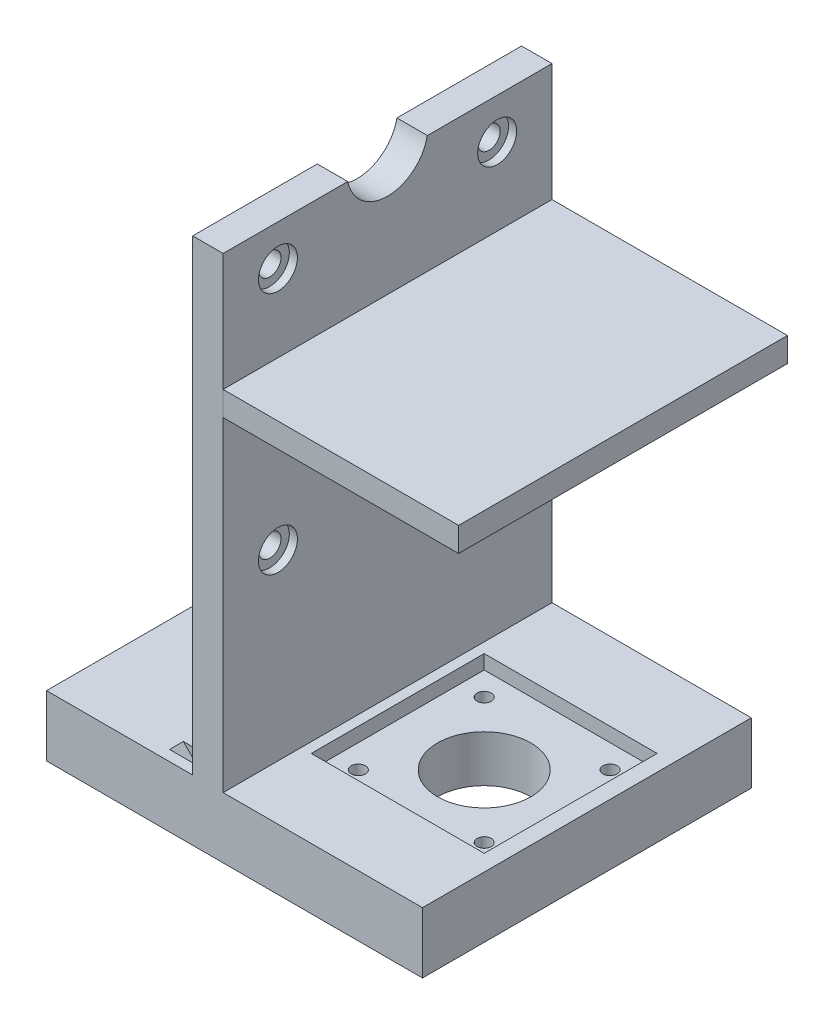
SolidWorks part; units mm, degrees
note: The reader was unsure of these and kept them because the rebuilt part matched: shared geometry of "Sketch11<5>", "Sketch13<3>", "Sketch21<2>".
ref_plane "Front Plane" through (0, 0, 0) normal (0, 0, 1) x (1, 0, 0)
ref_plane "Top Plane" through (0, 0, 0) normal (0, 1, 0) x (1, 0, 0)
ref_plane "Right Plane" through (0, 0, 0) normal (1, 0, 0) x (0, 0, -1)
sketch "Sketch1" plane through (0, 0, 0) normal (0, 1, 0) x (1, 0, 0)
  line L1 (-23.2, -27.5) -> (23.2, -27.5)
  line L2 (-23.2, -27.5) -> (-23.2, 27.5)
  line L3 (-23.2, 27.5) -> (23.2, 27.5)
  line L4 (23.2, -27.5) -> (23.2, 27.5)
  line L5 (-23.2, -27.5) -> (23.2, 27.5) construction
  line L6 (-23.2, 27.5) -> (23.2, -27.5) construction
  line L7 (-28.2, -33.5) -> (28.2, -33.5)
  line L8 (-28.2, -33.5) -> (-28.2, 33.5)
  line L9 (-28.2, 33.5) -> (28.2, 33.5)
  line L10 (28.2, -33.5) -> (28.2, 33.5)
  line L11 (-28.2, -33.5) -> (28.2, 33.5) construction
  line L12 (-28.2, 33.5) -> (28.2, -33.5) construction
  circle A0 centre (-2.9, 0) radius 4
  circle A1 centre (43.1, 0) radius 4
  point P0 (0, 0)
  point P6 (0, 0)
  dimension "D3" = 8
  dimension "D1" = 20.3
  dimension "D2" = 14.9
  dimension "D4" = 46
  dimension "D5" = 5
  dimension "D6" = 6
  dimension "D7" = 55
extrude "Boss-Extrude1" add sketch "Sketch1" along normal blind 14 contours L7 L10 L9 L8 L4 L1 L2 L3
sketch "Sketch4" plane through (0, 0, 0) normal (0, 1, 0) x (1, 0, 0)
  line L0 (-28.2, -33.5) -> (-40.2, -33.5)
  line L1 (-40.2, -33.5) -> (-40.2, -21.5)
  line L2 (-40.2, -21.5) -> (-28.2, -21.5)
  line L3 (-28.2, -33.5) -> (-28.2, 33.5) construction
  line L4 (-28.2, -21.5) -> (-28.2, -33.5)
  line L5 (-28.2, 33.5) -> (-40.2, 33.5)
  line L6 (-40.2, 33.5) -> (-40.2, 21.5)
  line L7 (-40.2, 21.5) -> (-28.2, 21.5)
  line L8 (-28.2, 21.5) -> (-28.2, 33.5)
  dimension "D1" = 12
  dimension "D2" = 12
extrude "Boss-Extrude2" add sketch "Sketch4" along normal blind 200
sketch "Sketch16" plane through (0, 0, -21.5) normal (0, 0, 1) x (1, 0, 0)
  line L0 (-40.2, 0) -> (-28.2, 0) construction
  line L1 (-28.2, 14) -> (-32.8, 14)
  line L2 (-28.2, 14) -> (-28.2, 0)
  line L3 (-28.2, 0) -> (-32.8, 0)
  line L4 (-32.8, 14) -> (-32.8, 0)
  dimension "D1" = 4.6
extrude "Boss-Extrude11" add sketch "Sketch16" along normal up to surface (43 mm away) up to face at (-33, 82.8, 21.5)
sketch "Sketch5" plane through (0, 200, 0) normal (0, 1, 0) x (1, 0, 0)
  line L0 (-28.2, -33.5) -> (28.2, -33.5) construction
  line L1 (-28.2, 33.5) -> (-23.2, 33.5)
  line L2 (-28.2, 33.5) -> (-28.2, -33.5)
  line L3 (-28.2, -33.5) -> (-23.2, -33.5)
  line L4 (-23.2, 33.5) -> (-23.2, -33.5)
  line L7 (-23.2, -27.5) -> (-23.2, 27.5) construction
extrude "Boss-Extrude3" add sketch "Sketch5" against normal blind 14
sketch "Sketch6" plane through (-40.2, 0, 0) normal (-1, 0, 0) x (0, 0, 1)
  line L0 (-21.5, 186) -> (21.5, 157.4103)
  line L1 (21.5, 200) -> (21.5, 0) construction
  line L2 (-21.5, 171.5897) -> (21.5, 143)
  line L3 (21.5, 143) -> (-21.5, 114.4103)
  line L4 (-21.5, 200) -> (-21.5, 0) construction
  line L5 (21.5, 128.5897) -> (-21.5, 100)
  line L6 (21.5, 157.4103) -> (21.5, 143)
  line L7 (21.5, 128.5897) -> (21.5, 143)
  line L8 (-21.5, 114.4103) -> (-21.5, 100)
  line L9 (-21.5, 186) -> (-21.5, 171.5897)
  line L10 (-21.5, 100) -> (21.5, 71.4103)
  line L11 (21.5, 71.4103) -> (21.5, 57)
  line L12 (21.5, 57) -> (-21.5, 85.5897)
  line L13 (-21.5, 85.5897) -> (-21.5, 100)
  line L14 (21.5, 57) -> (-21.5, 28.4103)
  line L15 (-21.5, 28.4103) -> (-21.5, 14)
  line L16 (-21.5, 14) -> (21.5, 42.5897)
  line L17 (21.5, 42.5897) -> (21.5, 57)
  line L18 (-21.5, 200) -> (-21.5, 186) construction
  line M18 (-21.5, 0) -> (-21.5, 200)
  dimension "D1" = 12
extrude "Boss-Extrude4" add sketch "Sketch6" against normal up to surface (12 mm away) contours L6 L0 L2 M18 | L5 L7 L3 M18 | L12 L11 L10 M18 | L16 L17 L14 M18 up to face at (-28.2, 100, 27.5)
sketch "Sketch2" plane through (28.2, 0, 0) normal (1, 0, 0) x (0, 0, -1)
  line L0 (-20.75, 7) -> (20.75, 7) construction
  line L1 (33.5, 14) -> (33.5, 0) construction
  circle A0 centre (-20.75, 7) radius 2.75
  circle A1 centre (20.75, 7) radius 2.75
  point P4 (33.5, 7)
  point P5 (0, 7)
  dimension "D1" = 5.5
  dimension "D2" = 41.5
extrude "Cut-Extrude1" cut sketch "Sketch2" against normal up to surface (5 mm away) up to face at (23.2, 7, 0)
sketch "Sketch3" plane through (-23.2, 0, 0) normal (1, 0, 0) x (0, 0, -1)
  line L0 (15.85, 7) -> (-15.85, 7) construction
  line L1 (-33.5, 14) -> (-33.5, 0) construction
  line L3 (-15.85, 7) -> (-33.5, 7) construction
  circle A0 centre (15.85, 7) radius 2.75
  circle A1 centre (-15.85, 7) radius 2.75
  point P0 (0, 7)
  dimension "D2" = 5.5
  dimension "D1" = 31.7
extrude "Cut-Extrude2" cut sketch "Sketch3" against normal through all
sketch "Sketch7" plane through (-23.2, 0, -32.7) normal (1, 0, 0) x (0, 0, -1)
  line L0 (-16.85, 193) -> (-48.55, 193) construction
  line L1 (-66.2, 200) -> (0.8, 200) construction
  line L2 (-66.2, 186) -> (-66.2, 200) construction
  line L3 (-48.55, 193) -> (-66.2, 193) construction
  circle A0 centre (-16.85, 193) radius 2.75
  circle A1 centre (-48.55, 193) radius 2.75
  point P0 (-32.7, 193)
  point P7 (-32.7, 200)
  point P13 (-66.2, 193)
  dimension "D2" = 5.5
  dimension "D1" = 31.7
extrude "Cut-Extrude3" cut sketch "Sketch7" against normal through all
ref_plane "Plane1" through (0, 215, 0) normal (0, 1, 0) x (1, 0, 0)
sketch "Sketch8" plane through (-23.2, 0, 0) normal (1, 0, 0) x (0, 0, -1)
  line L0 (-33.5, 186) -> (33.5, 186) construction
  line L1 (-33.5, 200) -> (-25.5, 200)
  line L2 (-33.5, 200) -> (-33.5, 186)
  line L3 (-33.5, 186) -> (-25.5, 186)
  line L4 (-25.5, 200) -> (-25.5, 186)
  line L6 (33.5, 200) -> (25.5, 200)
  line L7 (33.5, 200) -> (33.5, 186)
  line L8 (33.5, 186) -> (25.5, 186)
  line L9 (25.5, 200) -> (25.5, 186)
  dimension "D1" = 8
extrude "Boss-Extrude5" add sketch "Sketch8" along normal blind 1
sketch "Sketch9" plane through (0, 215, 0) normal (0, 1, 0) x (1, 0, 0)
  line L0 (-28.2, 21.5) -> (-28.2, -21.5) construction
  line L1 (-24.2, 40.5) -> (68.4, 40.5)
  line L2 (-24.2, 40.5) -> (-24.2, -40.5)
  line L3 (-24.2, -40.5) -> (68.4, -40.5)
  line L4 (68.4, 40.5) -> (68.4, -40.5)
  line L5 (-23.2, -25.5) -> (-23.2, 25.5) construction
  line L6 (-40.2, 33.5) -> (-40.2, 21.5) construction
  line L7 (-22.2, 40.5) -> (-15.4135, 40.5)
  line L8 (-22.2, 40.5) -> (-22.2, -40.5)
  line L9 (-22.2, -40.5) -> (-15.4135, -40.5)
  line L10 (-15.4135, 40.5) -> (-15.4135, -40.5)
  line L11 (-22.2, 33.5) -> (-22.2, 25.5) construction
  point P5 (68.4, 0)
  point P9 (-28.2, 0)
  point P10 (-24.2, 0)
  point P13 (43.1, 0)
  point P26 (-15.4135, 0)
  dimension "D1" = 81
  dimension "D2" = 25.3
  dimension "D3" = 66.3
  dimension "D4" = 81
  dimension "D5" = 16
extrude "Boss-Extrude6" add sketch "Sketch9" along normal blind 15 separate body contours L7 L10 L9 L8 L3 L2 L1 | L8 L1 L2 L3 | L1 L8 L3 L4
sketch "Sketch10" plane through (0, 230, 0) normal (0, 1, 0) x (1, 0, 0)
  line L1 (21.8, -21.3) -> (64.4, -21.3)
  line L2 (21.8, -21.3) -> (21.8, 21.3)
  line L3 (21.8, 21.3) -> (64.4, 21.3)
  line L4 (64.4, -21.3) -> (64.4, 21.3)
  line L5 (21.8, -21.3) -> (64.4, 21.3) construction
  line L6 (21.8, 21.3) -> (64.4, -21.3) construction
  line L8 (68.4, 40.5) -> (68.4, -40.5) construction
  point P0 (43.1, 0)
  point P13 (68.4, 0)
  dimension "D1" = 42.6
  dimension "D2" = 42.6
  dimension "D3" = 4
extrude "Cut-Extrude4" cut sketch "Sketch10" against normal blind 3.5
sketch "Sketch11" plane through (0, 226.5, -221.5) normal (0, -1, 0) x (1, 0, 0)
  line L0 (64.4, 200.2) -> (21.8, 200.2) construction
  line L1 (27.6, 206) -> (58.6, 206) construction
  line L2 (27.6, 206) -> (27.6, 237) construction
  line L3 (27.6, 237) -> (58.6, 237) construction
  line L4 (58.6, 206) -> (58.6, 237) construction
  line L5 (27.6, 206) -> (58.6, 237) construction
  line L6 (27.6, 237) -> (58.6, 206) construction
  line L7 (64.4, 242.8) -> (64.4, 200.2) construction
  circle A0 centre (27.6, 237) radius 1.75
  circle A1 centre (58.6, 237) radius 1.75
  circle A2 centre (58.6, 206) radius 1.75
  circle A3 centre (27.6, 206) radius 1.75
  circle A4 centre (27.6, 237) radius 3
  circle A5 centre (58.6, 237) radius 3
  circle A6 centre (58.6, 206) radius 3
  circle A7 centre (27.6, 206) radius 3
  circle A8 centre (43.1, 221.5) radius 11.5
  point P0 (43.1, 221.5)
  point P17 (43.1, 200.2)
  point P21 (64.4, 221.5)
  dimension "D1" = 3.5
  dimension "D4" = 6
  dimension "D5" = 23
  dimension "D2" = 31
  dimension "D3" = 31
extrude "Cut-Extrude5" cut sketch "Sketch11" along normal up to surface (11.5 mm away) contours A1 | A0 | A3 | A2 | A8
extrude "Cut-Extrude6" cut sketch "Sketch11<5>" against normal blind 3 from surface
sketch "Sketch11<5>" plane through (0, 226.5, -221.5) normal (0, -1, 0) x (1, 0, 0) same geometry as "Sketch11"
ref_plane "Plane2" through (11.8, 0, 0) normal (-1, 0, 0) x (0, 0, 1)
sketch "Sketch13" plane through (11.8, 0, 0) normal (-1, 0, 0) x (0, 0, 1)
  line L0 (0, 346.9575) -> (0, 351.8332) construction
  line L1 (-27, 275) -> (27, 275) construction
  line L2 (-27, 275) -> (-27, 335) construction
  line L3 (-27, 335) -> (27, 335) construction
  line L4 (27, 275) -> (27, 335) construction
  line L5 (-27, 275) -> (27, 335) construction
  line L6 (-27, 335) -> (27, 275) construction
  line L7 (-40.5, 345) -> (40.5, 345)
  line L8 (-40.5, 345) -> (-40.5, 230)
  line L9 (-40.5, 230) -> (40.5, 230)
  line L10 (40.5, 345) -> (40.5, 230)
  line L11 (-10, 346.9575) -> (-10, 351.8332)
  line L12 (10, 346.9575) -> (10, 351.8332)
  line L14 (25.5, 200) -> (-25.5, 200) construction
  line L16 (-40.5, 230) -> (40.5, 230) construction
  circle A0 centre (-27, 335) radius 2.75
  circle A1 centre (27, 335) radius 2.75
  circle A2 centre (27, 275) radius 2.75
  circle A3 centre (-27, 275) radius 2.75
  arc A4 (-10, 346.9575) -> (10, 346.9575) centre (0, 346.9575) ccw
  arc A5 (10, 351.8332) -> (-10, 351.8332) centre (0, 351.8332) ccw
  circle A6 centre (27, 335) radius 4.8
  circle A7 centre (27, 275) radius 4.8
  circle A8 centre (-27, 275) radius 4.8
  circle A9 centre (-27, 335) radius 4.8
  point P0 (0, 305)
  point P14 (0, 345)
  point P15 (0, 349.3954)
  point P25 (0, 342.1027)
  point P27 (0, 343.8299)
  point P28 (0, 345.8642)
  point P29 (0, 346.9575)
  point P32 (0, 200)
  dimension "D1" = 5.5
  dimension "D7" = 9.6
  dimension "D2" = 54
  dimension "D3" = 60
  dimension "D4" = 81
  dimension "D5" = 10
  dimension "D6" = 20
  dimension "D8" = 115
extrude "Boss-Extrude7" add sketch "Sketch13" against normal blind 5.5 separate body contours L10 L7 L8 L9 A3 L2 A0 L3 A1 L4 A2 L1 | A9 A0 | A6 A1 | A7 A2 | A8 A3
extrude "Boss-Extrude10" add sketch "Sketch13<3>" against normal blind 2 from surface at -5.5 contours A4 L11 L7 L8 L9 L10 L12 A9 A8 A7 A6
sketch "Sketch13<3>" plane through (11.8, 0, 0) normal (-1, 0, 0) x (0, 0, 1) same geometry as "Sketch13"
sketch "Sketch15" plane through (19.3, 0, 0) normal (1, 0, 0) x (0, 0, -1)
  line L1 (-40.5, 316) -> (40.5, 316)
  line L2 (-40.5, 316) -> (-40.5, 310)
  line L3 (-40.5, 310) -> (40.5, 310)
  line L4 (40.5, 316) -> (40.5, 310)
  line L7 (40.5, 230) -> (-40.5, 230) construction
  line L8 (-40.5, 345) -> (-40.5, 230) construction
  line L9 (40.5, 345) -> (40.5, 230) construction
  dimension "D1" = 80
  dimension "D2" = 6
extrude "Boss-Extrude9" add sketch "Sketch15" along normal blind 58
sketch "Sketch17" plane through (-24.2, 0, 0) normal (-1, 0, 0) x (0, 0, 1)
  line L1 (-79.0217, 207.6712) -> (80.383, 207.6712)
  line L2 (-79.0217, 207.6712) -> (-79.0217, -14.3434)
  line L3 (-79.0217, -14.3434) -> (80.383, -14.3434)
  line L4 (80.383, 207.6712) -> (80.383, -14.3434)
extrude "Cut-Extrude7" cut sketch "Sketch17" against normal through all both and the other way through all
sketch "Sketch18" plane through (-24.2, 0, 0) normal (-1, 0, 0) x (0, 0, 1)
  line L2 (-33.5, 225.2) -> (-18.5198, 225.2)
  line L3 (21.9441, 225.2) -> (34.1, 215)
  line L5 (-33.5, 215) -> (-40.5, 215)
  line L6 (-18.5198, 225.2) -> (-6.364, 215)
  line L7 (-6.364, 215) -> (14.964, 215)
  line L9 (6.964, 225.2) -> (21.9441, 225.2)
  line L11 (-33.5, 225.2) -> (-33.5, 219.7)
  line L12 (-33.5, 219.7) -> (-25.5, 219.7)
  line L13 (-25.5, 219.7) -> (-25.5, 215)
  line L14 (9.9, 215) -> (-9.9, 215) construction
  line L15 (-25.5, 215) -> (-33.5, 215)
  line L16 (6.964, 225.2) -> (6.964, 219.7)
  line L17 (6.964, 219.7) -> (14.964, 219.7)
  line L18 (14.964, 219.7) -> (14.964, 215)
  line L19 (34.1, 215) -> (40.5, 215)
  line L20 (-25.5, 215) -> (-6.364, 215)
  line L21 (14.964, 215) -> (34.1, 215)
  line M44 (-40.5, 215) -> (40.5, 215)
  dimension "D1" = 7
  dimension "D2" = 40
  dimension "D3" = 5.5
  dimension "D4" = 4.7
  dimension "D5" = 8
  dimension "D6" = 8.7
  dimension "D7" = 6.4
extrude "Cut-Extrude8" cut sketch "Sketch18" against normal blind 45 contours L12 L13 L6 L2 L11 M44 | L17 L18 L3 L9 L16 M44
sketch "Sketch19" plane through (0, 0, -40.5) normal (0, 0, -1) x (-1, 0, 0)
  line L0 (-11.8, 265) -> (23.2, 230)
  line L1 (-11.8, 345) -> (-11.8, 230) construction
  line L2 (24.2, 230) -> (-68.4, 230) construction
  line L3 (-11.8, 265) -> (-11.8, 230)
  line L4 (-11.8, 230) -> (23.2, 230)
  dimension "D1" = 35
  dimension "D2" = 35
extrude "Boss-Extrude13" add sketch "Sketch19" against normal blind 6
sketch "Sketch20" plane through (11.8, 0, 0) normal (-1, 0, 0) x (0, 0, 1)
  circle A0 centre (-27, 275) radius 12.5
  dimension "D1" = 25
sketch "Sketch21" plane through (0, 0, 40.5) normal (0, 0, 1) x (1, 0, 0)
  line L0 (11.8, 238.3) -> (16.1, 234)
  line L1 (11.8, 345) -> (11.8, 230) construction
  line L2 (16.1, 234) -> (16.1, 225.7)
  line L3 (16.1, 225.7) -> (7.8, 225.7)
  line L4 (7.8, 225.7) -> (3.5, 230)
  line L5 (11.8, 230) -> (-23.2, 230) construction
  line L6 (3.5, 230) -> (11.8, 230)
  line L7 (11.8, 230) -> (11.8, 238.3)
  dimension "D1" = 45
  dimension "D2" = 4.3
  dimension "D3" = 8.3
extrude "Cut-Extrude9" cut sketch "Sketch21" along normal blind 3.4 from offset 6 offset against normal yes
extrude "Cut-Extrude10" cut sketch "Sketch21<2>" along normal blind 3.4 from offset 43.5
sketch "Sketch21<2>" plane through (0, 0, 40.5) normal (0, 0, 1) x (1, 0, 0) same geometry as "Sketch21"
